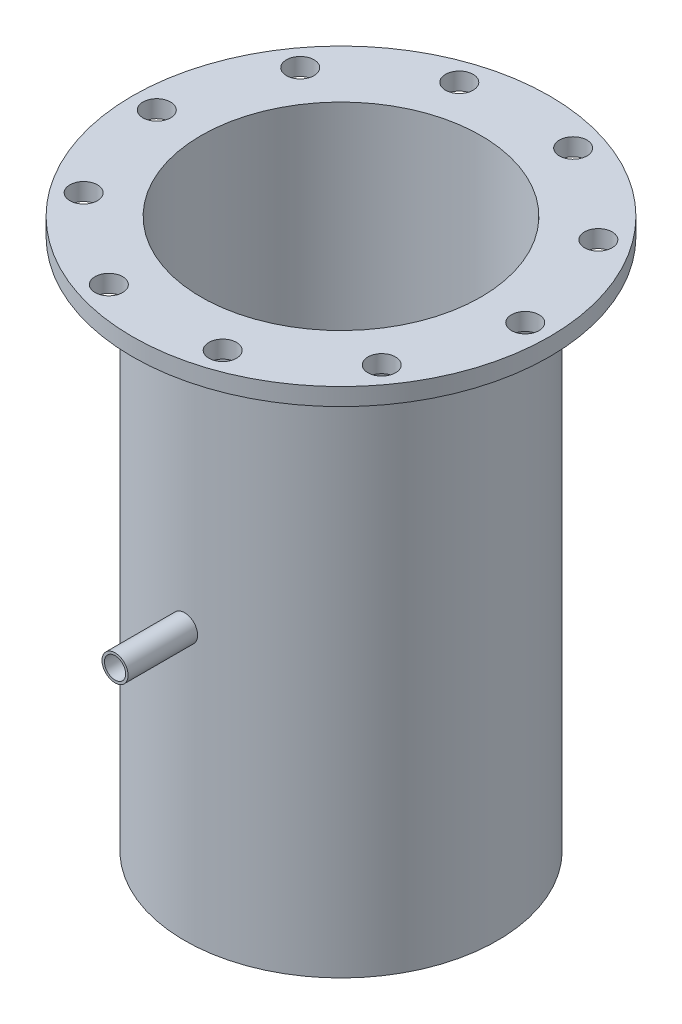
SolidWorks part; units mm, degrees
other "DetailItem1"
other "DetailItem2"
other "Weld Folder"
other "Weld Bead1"
other "Weld Bead2"
material "1023 Carbon Steel Sheet (SS)"
ref_plane "Front Plane" through (0, 0, 0) normal (0, 0, 1) x (1, 0, 0)
ref_plane "Top Plane" through (0, 0, 0) normal (0, 1, 0) x (1, 0, 0)
ref_plane "Right Plane" through (0, 0, 0) normal (1, 0, 0) x (0, 0, -1)
sketch "Sketch1" plane through (0, 0, 0) normal (0, 0, 1) x (1, 0, 0)
  line L0 (0, 0) -> (0, -134.8652) construction
  line L1 (51.1302, 0) -> (51.1302, -170.8058)
  line L2 (51.1302, -200.6) -> (57.15, -200.6)
  line L3 (57.15, -200.6) -> (57.15, -8.89)
  line L4 (54.61, -6.35) -> (76.2, -6.35)
  line L5 (76.2, -6.35) -> (76.2, 0)
  line L6 (76.2, 0) -> (51.1302, 0)
  line L7 (51.1302, -188.027) -> (53.848, -188.027)
  line L8 (53.848, -188.027) -> (53.848, -191.075)
  line L9 (53.848, -191.075) -> (51.1302, -191.075)
  line L10 (51.1302, -184.217) -> (53.6194, -184.217)
  line L11 (51.1302, -191.075) -> (51.1302, -200.6)
  line L12 (57.15, -8.89) -> (54.61, -6.35)
  line L13 (53.6194, -184.217) -> (53.6194, -179.4164)
  line L14 (53.6194, -179.4164) -> (51.1302, -179.4164)
  line L15 (-56.1848, -191.075) -> (56.1848, -191.075) construction
  line L16 (-50.1022, -191.075) -> (50.1022, -191.075) construction
  line L17 (51.1302, -184.217) -> (51.1302, -188.027)
  line L18 (51.1302, -175.6064) -> (53.6194, -175.6064)
  line L19 (53.6194, -175.6064) -> (53.6194, -170.8058)
  line L20 (53.6194, -170.8058) -> (51.1302, -170.8058)
  line L21 (51.1302, -175.6064) -> (51.1302, -179.4164)
  dimension "D1" = 51.1302
  dimension "D2" = 57.15
  dimension "D3" = 76.2
  dimension "D4" = 6.35
  dimension "D5" = 9.525
  dimension "D6" = 53.848
  dimension "D7" = 3.048
  dimension "D8" = 3.81
  dimension "D9" = 45
  dimension "D10" = 2.54
  dimension "D11" = 4.8006
  dimension "D12" = 53.6194
revolve "Revolve1" add sketch "Sketch1" angle 360 about L0
hole_wizard "Tap Drill for 3/8-16 Tap1" positions "Sketch2" profile "Sketch3" hole size "3/8" standard "ANSI Inch" end condition through all
sketch "Sketch2" plane through (0, 0, 0) normal (0, 1, 0) x (1, 0, 0)
  point P1 (67.31, 0)
  dimension "D1" = 67.31
sketch "Sketch3" plane through (67.31, 0, 0) normal (1, 0, 0) x (0, 0, 1)
  line L0 (0, 0) -> (0, 200.6)
  line L1 (0, 200.6) -> (5.0419, 200.6)
  line L2 (5.0419, 200.6) -> (5.0419, 0)
  line L5 (5.0419, 0) -> (0, 0)
  line L11 (0, -6.35) -> (0, 107.95) construction
  dimension "Thru Hole Dia." = 10.0838
  dimension "Thru Hole Depth" = 200.6
pattern_circular "CirPattern1" count 10 over 360 about axis through (0, 0, 0) along (0, 1, 0) of "Tap Drill for 3/8-16 Tap1"
ref_plane "Plane1" through (0, 0, 57.15) normal (0, 0, 1) x (1, 0, 0)
sketch "Sketch4" plane through (0, 0, 57.15) normal (0, 0, 1) x (1, 0, 0)
  circle A0 centre (0, -101.6) radius 4.7625
  circle A1 centre (0, -101.6) radius 3.8735
  dimension "D1" = 9.525
  dimension "D2" = 0.889
  dimension "D3" = 101.6
extrude "Boss-Extrude1" add sketch "Sketch4" along normal blind 25.4 separate body
hole_wizard "1/8 (0.125) Diameter Hole3" positions "3DSketch2" profile "Sketch11" hole size "1/8" standard "ANSI Inch"
sketch3d "3DSketch2"
  circle A0 centre (0, -101.6, 57.15) radius 4.1349 construction
  circle A1 centre (0, -101.6, 57.15) radius 4.7625 construction
  point P6 (0, -101.6, 61.2849)
  point P19 (0, -101.6, 61.9125)
  point P21 (0, -101.6, 57.15)
sketch "Sketch11" plane through (0, -101.6, 57.15) normal (1, 0, 0) x (0, -1, 0)
  line L0 (0, 0) -> (0, 26.3539)
  line L1 (0, 26.3539) -> (1.5875, 25.4)
  line L2 (1.5875, 25.4) -> (1.5875, 0)
  line L5 (1.5875, 0) -> (0, 0)
  line L10 (0, 26.3539) -> (-1.5875, 25.4) construction
  line L11 (0, -6.35) -> (0, 107.95) construction
  dimension "Hole Dia." = 3.175
  dimension "Hole Depth" = 25.4
  dimension "Drill Angle" = 118
